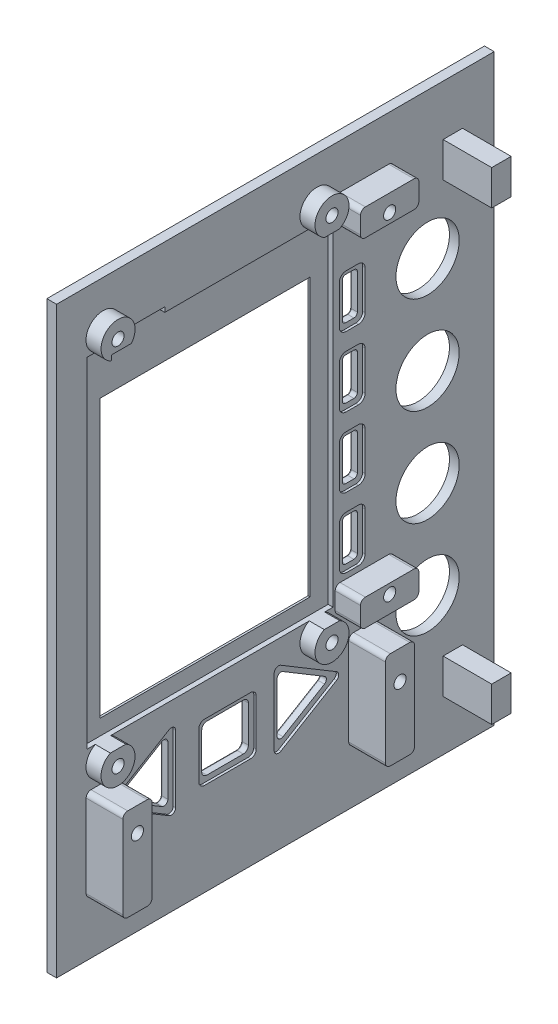
SolidWorks part; units mm, degrees
ref_plane "Front Plane" through (0, 0, 0) normal (0, 0, 1) x (1, 0, 0)
ref_plane "Top Plane" through (0, 0, 0) normal (0, 1, 0) x (1, 0, 0)
ref_plane "Right Plane" through (0, 0, 0) normal (1, 0, 0) x (0, 0, -1)
ref_plane "Plane2" through (-1175.0489, 0, 0) normal (-1, 0, 0) x (0, 0, 1)
sketch "Sketch2" plane through (-1175.0489, 0, 0) normal (-1, 0, 0) x (0, 0, 1)
  line L0 (-1289.195, -889.2833) -> (-1289.195, -789.2833) construction
  line L1 (-1204.195, -779.2833) -> (-1294.195, -779.2833)
  line L2 (-1204.195, -779.2833) -> (-1204.195, -899.2833)
  line L3 (-1204.195, -899.2833) -> (-1294.195, -899.2833)
  line L4 (-1294.195, -779.2833) -> (-1294.195, -899.2833)
  line L5 (-1289.195, -889.2833) -> (-1287.685, -889.2833) construction
  line L6 (-1289.195, -789.2833) -> (-1287.685, -789.2833) construction
  circle A0 centre (-1280.5, -869.2833) radius 6.5
  circle A1 centre (-1280.5, -849.2833) radius 6.5
  circle A2 centre (-1280.5, -829.2833) radius 6.5
  circle A3 centre (-1280.5, -809.2833) radius 6.5
  ellipse E0 centre (-1280.5, -869.2833) end of major axis (-1280.0404, -869.7429) minor radius 0.65 construction
  ellipse E1 centre (-1280.5, -849.2833) end of major axis (-1280.0404, -849.7429) minor radius 0.65 construction
  ellipse E2 centre (-1280.5, -829.2833) end of major axis (-1280.0404, -829.7429) minor radius 0.65 construction
  ellipse E3 centre (-1280.5, -809.2833) end of major axis (-1280.0404, -809.7429) minor radius 0.65 construction
  ellipse E4 centre (-1280.5, -869.2833) end of major axis (-1280.0404, -869.7429) minor radius 0.65
  ellipse E5 centre (-1280.5, -849.2833) end of major axis (-1280.0404, -849.7429) minor radius 0.65 construction
  ellipse E6 centre (-1280.5, -829.2833) end of major axis (-1280.0404, -829.7429) minor radius 0.65
  ellipse E7 centre (-1280.5, -809.2833) end of major axis (-1280.0404, -809.7429) minor radius 0.65
  dimension "D5" = 13
  dimension "D6" = 13
  dimension "D7" = 13
  dimension "D8" = 13
  dimension "D1" = 5
  dimension "D2" = 10
  dimension "D3" = 10
  dimension "D4" = 90
extrude "Boss-Extrude2" add sketch "Sketch2" along normal blind 2 contours L1 L4 L3 L2 A3 A2 A1 A0 region at (-1175.0489, -839.2833, -1247.5765)
sketch "Sketch3" plane through (-1177.0489, 0, 0) normal (-1, 0, 0) x (0, 0, 1)
  line L12 (-1214.15, -858.4833) -> (-1257.35, -858.4833) construction
  line L13 (-1257.35, -858.4833) -> (-1257.35, -801.5033) construction
  line L14 (-1214.15, -801.5033) -> (-1214.15, -858.4833) construction
  line L15 (-1257.35, -801.5033) -> (-1214.15, -801.5033) construction
  line L16 (-1214.15, -858.4833) -> (-1257.35, -858.4833)
  line L17 (-1257.35, -858.4833) -> (-1257.35, -801.5033)
  line L18 (-1214.15, -801.5033) -> (-1214.15, -858.4833)
  line L19 (-1257.35, -801.5033) -> (-1214.15, -801.5033)
extrude "tft_cutout" cut sketch "Sketch3" against normal through all
sketch "tft_inset_cutout" plane through (-1175.0489, 0, 0) normal (1, 0, 0) x (0, 0, -1)
  line L4 (1210.95, -792.3623) -> (1210.95, -861.1623) construction
  line L5 (1260.55, -792.3623) -> (1210.95, -792.3623) construction
  line L12 (1260.55, -861.1623) -> (1260.55, -792.3623) construction
  line L17 (1210.95, -861.1623) -> (1260.55, -861.1623) construction
  line L18 (1260.55, -861.1623) -> (1260.55, -792.3623) construction
  line L19 (1210.95, -861.1623) -> (1260.55, -861.1623) construction
  line L20 (1210.95, -792.3623) -> (1210.95, -861.1623) construction
  line L21 (1260.55, -792.3623) -> (1210.95, -792.3623) construction
  line L22 (1261.05, -791.8623) -> (1210.45, -791.8623)
  line L26 (1212.45, -792.3623) -> (1226.45, -792.3623)
  line L27 (1212.45, -792.3623) -> (1212.45, -790.8623)
  line L28 (1212.45, -790.8623) -> (1226.45, -790.8623)
  line L29 (1226.45, -792.3623) -> (1226.45, -790.8623)
  line L30 (1210.45, -791.8623) -> (1210.45, -861.6623)
  line L31 (1210.45, -861.6623) -> (1261.05, -861.6623)
  line L32 (1261.05, -861.6623) -> (1261.05, -791.8623)
  line M40 (1257.35, -858.4833) -> (1214.15, -858.4833)
  line M41 (1214.15, -858.4833) -> (1214.15, -801.5033)
  line M42 (1214.15, -801.5033) -> (1257.35, -801.5033)
  line M43 (1257.35, -801.5033) -> (1257.35, -858.4833)
  dimension "D3" = 1.5
  dimension "D4" = 0.5
  dimension "D1" = 14
  dimension "D2" = 1.5
extrude "Cut-Extrude2" cut sketch "tft_inset_cutout" against normal up to surface (1 mm away) contours L18 | L31 L32 L22 L29 L26 L27 L30 M43 M40 M41 M42 | L26 L29 L22 L27 | L22 L29 L28 L27 region at (-1175.0489, -826.7623, -1260.1879) region at (-1175.0489, -792.1123, -1219.45) region at (-1175.0489, -791.3623, -1219.45)
chamfer "Chamfer2" distance 1 angle 30 4 edges at (-1177.0489, -829.9933, -1257.35) (-1177.0489, -858.4833, -1235.75) (-1177.0489, -829.9933, -1214.15) (-1177.0489, -801.5033, -1235.75) first distance on face at (-1177.0489, -829.9933, -1235.75)
sketch "Sketch6" plane through (-1175.0489, 0, 0) normal (1, 0, 0) x (0, 0, -1)
  line L5 (1261.5, -863.4916) -> (1273.5, -863.4916)
  line L6 (1261.5, -863.4916) -> (1261.5, -857.9916)
  line L7 (1261.5, -857.9916) -> (1273.5, -857.9916)
  line L8 (1261.5, -863.4916) -> (1273.5, -863.4916)
  line L9 (1273.5, -863.4916) -> (1273.5, -788.4916)
  line L10 (1273.5, -788.4916) -> (1261.5, -788.4916)
  line L11 (1261.5, -788.4916) -> (1261.5, -863.4916)
  line L12 (1261.5, -863.4916) -> (1273.5, -863.4916) construction
  line L13 (1273.5, -863.4916) -> (1273.5, -788.4916) construction
  line L14 (1273.5, -788.4916) -> (1261.5, -788.4916) construction
  line L15 (1261.5, -788.4916) -> (1261.5, -863.4916) construction
  line L16 (1273.5, -863.4916) -> (1273.5, -857.9916)
  line L17 (1261.5, -788.4916) -> (1273.5, -788.4916)
  line L18 (1261.5, -788.4916) -> (1261.5, -793.9916)
  line L19 (1261.5, -793.9916) -> (1273.5, -793.9916)
  line L20 (1273.5, -788.4916) -> (1273.5, -793.9916)
  circle A0 centre (1267.5, -859.9916) radius 1.25 construction
  circle A1 centre (1267.5, -859.9916) radius 1.25 construction
  circle A2 centre (1267.5, -859.9916) radius 1.25
  circle A3 centre (1267.5, -791.9916) radius 1.25 construction
  circle A4 centre (1267.5, -791.9916) radius 1.25 construction
  circle A5 centre (1267.5, -791.9916) radius 1.25
  dimension "D2" = 2.5
  dimension "D4" = 2.5
  dimension "D3" = 2
  dimension "D5" = 2
extrude "menu_standoffs" add sketch "Sketch6" along normal up to surface (5.203 mm away)
fillet "Fillet1" radius 1 8 edges at (-1172.4474, -793.9916, -1261.5) (-1172.4474, -793.9916, -1273.5) (-1172.4474, -788.4916, -1273.5) (-1172.4474, -788.4916, -1261.5) (-1172.4474, -857.9916, -1273.5) (-1172.4474, -857.9916, -1261.5) (-1172.4474, -863.4916, -1261.5) (-1172.4474, -863.4916, -1273.5)
sketch "Sketch7" plane through (-1169.8459, 0, 0) normal (1, 0, 0) x (0, 0, -1)
  circle A0 centre (1267.5, -859.9916) radius 1.25 construction
  circle A1 centre (1267.5, -791.9916) radius 1.25 construction
  circle A2 centre (1267.5, -859.9916) radius 1.25
  circle A3 centre (1267.5, -791.9916) radius 1.25
extrude "menu_standoff_holes" [suppressed] cut sketch "Sketch7" against normal blind 5 contours A2
sketch "Sketch8" plane through (-1175.0489, 0, 0) normal (1, 0, 0) x (0, 0, -1)
  circle A0 centre (1213.75, -864.7833) radius 1.55 construction
  circle A1 centre (1257.75, -864.7833) radius 1.55 construction
  circle A2 centre (1257.75, -788.7033) radius 1.55 construction
  circle A3 centre (1213.75, -788.7036) radius 1.55 construction
  circle A4 centre (1213.75, -864.7833) radius 1.55 construction
  circle A5 centre (1257.75, -864.7833) radius 1.55 construction
  circle A6 centre (1257.75, -788.7033) radius 1.55 construction
  circle A7 centre (1213.75, -788.7036) radius 1.55 construction
  circle A8 centre (1213.75, -788.7036) radius 3.5
  circle A9 centre (1257.75, -788.7033) radius 3.5
  circle A10 centre (1257.75, -864.7833) radius 3.5
  circle A11 centre (1213.75, -864.7833) radius 3.5
  circle A12 centre (1213.75, -788.7036) radius 1.25
  circle A13 centre (1213.75, -864.7833) radius 1.25
  circle A14 centre (1257.75, -864.7833) radius 1.25
  circle A15 centre (1257.75, -788.7033) radius 1.25
  dimension "D2" = 2.5
  dimension "D1" = 7
extrude "TFT_standoffs" add sketch "Sketch8" along normal up to surface (3.09 mm away)
sketch "Sketch9" plane through (-1175.0489, 0, 0) normal (1, 0, 0) x (0, 0, -1)
  circle A0 centre (1213.75, -788.7036) radius 1.25 construction
  circle A1 centre (1213.75, -864.7833) radius 1.25 construction
  circle A2 centre (1257.75, -864.7833) radius 1.25 construction
  circle A3 centre (1257.75, -788.7033) radius 1.25 construction
  circle A4 centre (1213.75, -788.7036) radius 1.25
  circle A5 centre (1213.75, -864.7833) radius 1.25
  circle A6 centre (1257.75, -864.7833) radius 1.25
  circle A7 centre (1257.75, -788.7033) radius 1.25
extrude "TFT_standoff_holes" cut sketch "Sketch9" against normal offset from surface (1 mm away) 1 up to face at (-1177.0489, -829.9933, -1235.75)
extrude "Cut-Extrude5" cut sketch "Sketch5<3>" along normal through all contours L31 L32 L22 L29 L26 L27 L30 M43 M40 M41 M42 | L22 L29 L28 L27 | L26 L29 L22 L27 region at (-1175.0489, -826.7623, -1260.1879) region at (-1175.0489, -792.1123, -1219.45) region at (-1175.0489, -791.3623, -1219.45)
sketch "Sketch5<3>" plane through (-1175.0489, 0, 0) normal (1, 0, 0) x (0, 0, -1) same geometry as "tft_inset_cutout"
sketch "Sketch10" plane through (-1175.0489, 0, 0) normal (1, 0, 0) x (0, 0, -1)
  line L0 (1267.2535, -804.4983) -> (1267.2535, -812.4983) construction
  line L1 (1266.2535, -813.4983) -> (1263.7535, -813.4983) construction
  line L2 (1262.7535, -812.4983) -> (1262.7535, -804.4983) construction
  line L3 (1263.7535, -803.4983) -> (1266.2535, -803.4983) construction
  line L4 (1267.2535, -804.4983) -> (1267.2535, -812.4983) construction
  line L5 (1266.2535, -813.4983) -> (1263.7535, -813.4983) construction
  line L6 (1262.7535, -812.4983) -> (1262.7535, -804.4983) construction
  line L7 (1263.7535, -803.4983) -> (1266.2535, -803.4983) construction
  line L8 (1267.6535, -804.4983) -> (1267.6535, -812.4983)
  line L9 (1266.2535, -813.8983) -> (1263.7535, -813.8983)
  line L10 (1262.3535, -812.4983) -> (1262.3535, -804.4983)
  line L11 (1263.7535, -803.0983) -> (1266.2535, -803.0983)
  line L12 (1267.6535, -818.8283) -> (1267.6535, -826.8283)
  line L13 (1266.2535, -828.2283) -> (1263.7535, -828.2283)
  line L14 (1262.3535, -826.8283) -> (1262.3535, -818.8283)
  line L15 (1263.7535, -817.4283) -> (1266.2535, -817.4283)
  line L16 (1267.2535, -818.8283) -> (1267.2535, -826.8283) construction
  line L17 (1266.2535, -827.8283) -> (1263.7535, -827.8283) construction
  line L18 (1262.7535, -826.8283) -> (1262.7535, -818.8283) construction
  line L19 (1263.7535, -817.8283) -> (1266.2535, -817.8283) construction
  line L20 (1267.6535, -833.1583) -> (1267.6535, -841.1583)
  line L21 (1266.2535, -842.5583) -> (1263.7535, -842.5583)
  line L22 (1262.3535, -841.1583) -> (1262.3535, -833.1583)
  line L23 (1263.7535, -831.7583) -> (1266.2535, -831.7583)
  line L24 (1267.2535, -833.1583) -> (1267.2535, -841.1583) construction
  line L25 (1266.2535, -842.1583) -> (1263.7535, -842.1583) construction
  line L26 (1262.7535, -841.1583) -> (1262.7535, -833.1583) construction
  line L27 (1263.7535, -832.1583) -> (1266.2535, -832.1583) construction
  line L28 (1267.6535, -847.4883) -> (1267.6535, -855.4883)
  line L29 (1266.2535, -856.8883) -> (1263.7535, -856.8883)
  line L30 (1262.3535, -855.4883) -> (1262.3535, -847.4883)
  line L31 (1263.7535, -846.0883) -> (1266.2535, -846.0883)
  line L32 (1267.2535, -847.4883) -> (1267.2535, -855.4883) construction
  line L33 (1266.2535, -856.4883) -> (1263.7535, -856.4883) construction
  line L34 (1262.7535, -855.4883) -> (1262.7535, -847.4883) construction
  line L35 (1263.7535, -846.4883) -> (1266.2535, -846.4883) construction
  arc A0 (1267.2535, -804.4983) -> (1266.2535, -803.4983) centre (1266.2535, -804.4983) ccw construction
  arc A1 (1266.2535, -813.4983) -> (1267.2535, -812.4983) centre (1266.2535, -812.4983) ccw construction
  arc A2 (1262.7535, -812.4983) -> (1263.7535, -813.4983) centre (1263.7535, -812.4983) ccw construction
  arc A3 (1263.7535, -803.4983) -> (1262.7535, -804.4983) centre (1263.7535, -804.4983) ccw construction
  arc A4 (1267.2535, -804.4983) -> (1266.2535, -803.4983) centre (1266.2535, -804.4983) ccw construction
  arc A5 (1266.2535, -813.4983) -> (1267.2535, -812.4983) centre (1266.2535, -812.4983) ccw construction
  arc A6 (1262.7535, -812.4983) -> (1263.7535, -813.4983) centre (1263.7535, -812.4983) ccw construction
  arc A7 (1263.7535, -803.4983) -> (1262.7535, -804.4983) centre (1263.7535, -804.4983) ccw construction
  arc A8 (1266.2535, -813.8983) -> (1267.6535, -812.4983) centre (1266.2535, -812.4983) ccw
  arc A9 (1262.3535, -812.4983) -> (1263.7535, -813.8983) centre (1263.7535, -812.4983) ccw
  arc A10 (1263.7535, -803.0983) -> (1262.3535, -804.4983) centre (1263.7535, -804.4983) ccw
  arc A11 (1267.6535, -804.4983) -> (1266.2535, -803.0983) centre (1266.2535, -804.4983) ccw
  arc A12 (1266.2535, -828.2283) -> (1267.6535, -826.8283) centre (1266.2535, -826.8283) ccw
  arc A13 (1262.3535, -826.8283) -> (1263.7535, -828.2283) centre (1263.7535, -826.8283) ccw
  arc A14 (1263.7535, -817.4283) -> (1262.3535, -818.8283) centre (1263.7535, -818.8283) ccw
  arc A15 (1267.6535, -818.8283) -> (1266.2535, -817.4283) centre (1266.2535, -818.8283) ccw
  arc A16 (1267.2535, -818.8283) -> (1266.2535, -817.8283) centre (1266.2535, -818.8283) ccw construction
  arc A17 (1266.2535, -827.8283) -> (1267.2535, -826.8283) centre (1266.2535, -826.8283) ccw construction
  arc A18 (1262.7535, -826.8283) -> (1263.7535, -827.8283) centre (1263.7535, -826.8283) ccw construction
  arc A19 (1263.7535, -817.8283) -> (1262.7535, -818.8283) centre (1263.7535, -818.8283) ccw construction
  arc A20 (1266.2535, -842.5583) -> (1267.6535, -841.1583) centre (1266.2535, -841.1583) ccw
  arc A21 (1262.3535, -841.1583) -> (1263.7535, -842.5583) centre (1263.7535, -841.1583) ccw
  arc A22 (1263.7535, -831.7583) -> (1262.3535, -833.1583) centre (1263.7535, -833.1583) ccw
  arc A23 (1267.6535, -833.1583) -> (1266.2535, -831.7583) centre (1266.2535, -833.1583) ccw
  arc A24 (1267.2535, -833.1583) -> (1266.2535, -832.1583) centre (1266.2535, -833.1583) ccw construction
  arc A25 (1266.2535, -842.1583) -> (1267.2535, -841.1583) centre (1266.2535, -841.1583) ccw construction
  arc A26 (1262.7535, -841.1583) -> (1263.7535, -842.1583) centre (1263.7535, -841.1583) ccw construction
  arc A27 (1263.7535, -832.1583) -> (1262.7535, -833.1583) centre (1263.7535, -833.1583) ccw construction
  arc A28 (1266.2535, -856.8883) -> (1267.6535, -855.4883) centre (1266.2535, -855.4883) ccw
  arc A29 (1262.3535, -855.4883) -> (1263.7535, -856.8883) centre (1263.7535, -855.4883) ccw
  arc A30 (1263.7535, -846.0883) -> (1262.3535, -847.4883) centre (1263.7535, -847.4883) ccw
  arc A31 (1267.6535, -847.4883) -> (1266.2535, -846.0883) centre (1266.2535, -847.4883) ccw
  arc A32 (1267.2535, -847.4883) -> (1266.2535, -846.4883) centre (1266.2535, -847.4883) ccw construction
  arc A33 (1266.2535, -856.4883) -> (1267.2535, -855.4883) centre (1266.2535, -855.4883) ccw construction
  arc A34 (1262.7535, -855.4883) -> (1263.7535, -856.4883) centre (1263.7535, -855.4883) ccw construction
  arc A35 (1263.7535, -846.4883) -> (1262.7535, -847.4883) centre (1263.7535, -847.4883) ccw construction
  dimension "D1" = 0.4
  dimension "D2" = 4
extrude "menu_panel_inset" cut sketch "Sketch10" against normal offset from surface 1.5 and the other way through all up to face at (-1177.0489, -829.9933, -1235.75)
sketch "Sketch11" plane through (-1177.0489, 0, 0) normal (-1, 0, 0) x (0, 0, 1)
  line L0 (-1265.8535, -812.4983) -> (-1264.1535, -812.4983) construction
  line L1 (-1266.2535, -804.8983) -> (-1266.2535, -812.0983) construction
  line L2 (-1265.8535, -804.4983) -> (-1264.1535, -804.4983) construction
  line L3 (-1263.7535, -804.8983) -> (-1263.7535, -812.0983) construction
  line L4 (-1265.8535, -812.4983) -> (-1264.1535, -812.4983) construction
  line L5 (-1266.2535, -804.8983) -> (-1266.2535, -812.0983) construction
  line L6 (-1265.8535, -804.4983) -> (-1264.1535, -804.4983) construction
  line L7 (-1263.7535, -804.8983) -> (-1263.7535, -812.0983) construction
  line L8 (-1263.4535, -804.8983) -> (-1263.4535, -812.0983)
  line L9 (-1265.8535, -812.7983) -> (-1264.1535, -812.7983)
  line L10 (-1266.5535, -804.8983) -> (-1266.5535, -812.0983)
  line L11 (-1265.8535, -804.1983) -> (-1264.1535, -804.1983)
  line L12 (-1263.4535, -819.2283) -> (-1263.4535, -826.4283)
  line L13 (-1265.8535, -827.1283) -> (-1264.1535, -827.1283)
  line L14 (-1266.5535, -819.2283) -> (-1266.5535, -826.4283)
  line L15 (-1265.8535, -818.5283) -> (-1264.1535, -818.5283)
  line L16 (-1265.8535, -826.8283) -> (-1264.1535, -826.8283) construction
  line L17 (-1266.2535, -819.2283) -> (-1266.2535, -826.4283) construction
  line L18 (-1265.8535, -818.8283) -> (-1264.1535, -818.8283) construction
  line L19 (-1263.7535, -819.2283) -> (-1263.7535, -826.4283) construction
  line L20 (-1263.4535, -833.5583) -> (-1263.4535, -840.7583)
  line L21 (-1265.8535, -841.4583) -> (-1264.1535, -841.4583)
  line L22 (-1266.5535, -833.5583) -> (-1266.5535, -840.7583)
  line L23 (-1265.8535, -832.8583) -> (-1264.1535, -832.8583)
  line L24 (-1265.8535, -841.1583) -> (-1264.1535, -841.1583) construction
  line L25 (-1266.2535, -833.5583) -> (-1266.2535, -840.7583) construction
  line L26 (-1265.8535, -833.1583) -> (-1264.1535, -833.1583) construction
  line L27 (-1263.7535, -833.5583) -> (-1263.7535, -840.7583) construction
  line L28 (-1263.4535, -847.8883) -> (-1263.4535, -855.0883)
  line L29 (-1265.8535, -855.7883) -> (-1264.1535, -855.7883)
  line L30 (-1266.5535, -847.8883) -> (-1266.5535, -855.0883)
  line L31 (-1265.8535, -847.1883) -> (-1264.1535, -847.1883)
  line L32 (-1265.8535, -855.4883) -> (-1264.1535, -855.4883) construction
  line L33 (-1266.2535, -847.8883) -> (-1266.2535, -855.0883) construction
  line L34 (-1265.8535, -847.4883) -> (-1264.1535, -847.4883) construction
  line L35 (-1263.7535, -847.8883) -> (-1263.7535, -855.0883) construction
  arc A0 (-1264.1535, -812.4983) -> (-1263.7535, -812.0983) centre (-1264.1535, -812.0983) ccw construction
  arc A1 (-1266.2535, -812.0983) -> (-1265.8535, -812.4983) centre (-1265.8535, -812.0983) ccw construction
  arc A2 (-1265.8535, -804.4983) -> (-1266.2535, -804.8983) centre (-1265.8535, -804.8983) ccw construction
  arc A3 (-1263.7535, -804.8983) -> (-1264.1535, -804.4983) centre (-1264.1535, -804.8983) ccw construction
  arc A4 (-1264.1535, -812.4983) -> (-1263.7535, -812.0983) centre (-1264.1535, -812.0983) ccw construction
  arc A5 (-1266.2535, -812.0983) -> (-1265.8535, -812.4983) centre (-1265.8535, -812.0983) ccw construction
  arc A6 (-1265.8535, -804.4983) -> (-1266.2535, -804.8983) centre (-1265.8535, -804.8983) ccw construction
  arc A7 (-1263.7535, -804.8983) -> (-1264.1535, -804.4983) centre (-1264.1535, -804.8983) ccw construction
  arc A8 (-1264.1535, -812.7983) -> (-1263.4535, -812.0983) centre (-1264.1535, -812.0983) ccw
  arc A9 (-1266.5535, -812.0983) -> (-1265.8535, -812.7983) centre (-1265.8535, -812.0983) ccw
  arc A10 (-1265.8535, -804.1983) -> (-1266.5535, -804.8983) centre (-1265.8535, -804.8983) ccw
  arc A11 (-1263.4535, -804.8983) -> (-1264.1535, -804.1983) centre (-1264.1535, -804.8983) ccw
  arc A12 (-1264.1535, -827.1283) -> (-1263.4535, -826.4283) centre (-1264.1535, -826.4283) ccw
  arc A13 (-1266.5535, -826.4283) -> (-1265.8535, -827.1283) centre (-1265.8535, -826.4283) ccw
  arc A14 (-1265.8535, -818.5283) -> (-1266.5535, -819.2283) centre (-1265.8535, -819.2283) ccw
  arc A15 (-1263.4535, -819.2283) -> (-1264.1535, -818.5283) centre (-1264.1535, -819.2283) ccw
  arc A16 (-1264.1535, -826.8283) -> (-1263.7535, -826.4283) centre (-1264.1535, -826.4283) ccw construction
  arc A17 (-1266.2535, -826.4283) -> (-1265.8535, -826.8283) centre (-1265.8535, -826.4283) ccw construction
  arc A18 (-1265.8535, -818.8283) -> (-1266.2535, -819.2283) centre (-1265.8535, -819.2283) ccw construction
  arc A19 (-1263.7535, -819.2283) -> (-1264.1535, -818.8283) centre (-1264.1535, -819.2283) ccw construction
  arc A20 (-1264.1535, -841.4583) -> (-1263.4535, -840.7583) centre (-1264.1535, -840.7583) ccw
  arc A21 (-1266.5535, -840.7583) -> (-1265.8535, -841.4583) centre (-1265.8535, -840.7583) ccw
  arc A22 (-1265.8535, -832.8583) -> (-1266.5535, -833.5583) centre (-1265.8535, -833.5583) ccw
  arc A23 (-1263.4535, -833.5583) -> (-1264.1535, -832.8583) centre (-1264.1535, -833.5583) ccw
  arc A24 (-1264.1535, -841.1583) -> (-1263.7535, -840.7583) centre (-1264.1535, -840.7583) ccw construction
  arc A25 (-1266.2535, -840.7583) -> (-1265.8535, -841.1583) centre (-1265.8535, -840.7583) ccw construction
  arc A26 (-1265.8535, -833.1583) -> (-1266.2535, -833.5583) centre (-1265.8535, -833.5583) ccw construction
  arc A27 (-1263.7535, -833.5583) -> (-1264.1535, -833.1583) centre (-1264.1535, -833.5583) ccw construction
  arc A28 (-1264.1535, -855.7883) -> (-1263.4535, -855.0883) centre (-1264.1535, -855.0883) ccw
  arc A29 (-1266.5535, -855.0883) -> (-1265.8535, -855.7883) centre (-1265.8535, -855.0883) ccw
  arc A30 (-1265.8535, -847.1883) -> (-1266.5535, -847.8883) centre (-1265.8535, -847.8883) ccw
  arc A31 (-1263.4535, -847.8883) -> (-1264.1535, -847.1883) centre (-1264.1535, -847.8883) ccw
  arc A32 (-1264.1535, -855.4883) -> (-1263.7535, -855.0883) centre (-1264.1535, -855.0883) ccw construction
  arc A33 (-1266.2535, -855.0883) -> (-1265.8535, -855.4883) centre (-1265.8535, -855.0883) ccw construction
  arc A34 (-1265.8535, -847.4883) -> (-1266.2535, -847.8883) centre (-1265.8535, -847.8883) ccw construction
  arc A35 (-1263.7535, -847.8883) -> (-1264.1535, -847.4883) centre (-1264.1535, -847.8883) ccw construction
  dimension "D1" = 0.3
  dimension "D2" = 4
extrude "menu_panel_cutout" cut sketch "Sketch11" against normal through all
fillet "Fillet2" radius 0.25 32 edges at (-1177.0489, -808.4983, -1263.4535) (-1177.0489, -812.5933, -1263.6586) (-1177.0489, -812.7983, -1265.0035) (-1177.0489, -812.5933, -1266.3485) (-1177.0489, -808.4983, -1266.5535) (-1177.0489, -804.4033, -1266.3485) (-1177.0489, -804.1983, -1265.0035) (-1177.0489, -827.1283, -1265.0035) (-1177.0489, -826.9233, -1266.3485) (-1177.0489, -822.8283, -1266.5535) (-1177.0489, -818.7333, -1266.3485) (-1177.0489, -818.5283, -1265.0035) (-1177.0489, -818.7333, -1263.6586) (-1177.0489, -822.8283, -1263.4535) (-1177.0489, -841.4583, -1265.0035) (-1177.0489, -841.2533, -1266.3485) (-1177.0489, -837.1583, -1266.5535) (-1177.0489, -833.0633, -1266.3485) (-1177.0489, -832.8583, -1265.0035) (-1177.0489, -833.0633, -1263.6586) (-1177.0489, -837.1583, -1263.4535) (-1177.0489, -851.4883, -1263.4535) (-1177.0489, -855.5833, -1263.6586) (-1177.0489, -855.7883, -1265.0035) (-1177.0489, -855.5833, -1266.3485) (-1177.0489, -851.4883, -1266.5535) (-1177.0489, -847.3933, -1266.3485) (-1177.0489, -847.1883, -1265.0035) (-1177.0489, -804.4033, -1263.6586) (-1177.0489, -826.9233, -1263.6586) (-1177.0489, -841.2533, -1263.6586) (-1177.0489, -847.3933, -1263.6586)
sketch "Sketch12" plane through (-1175.0489, 0, 0) normal (1, 0, 0) x (0, 0, -1)
  line L0 (1270.2797, -888.2833) -> (1210.2797, -888.2833) construction
  line L1 (1270.2797, -868.2833) -> (1264.2797, -868.2833)
  line L2 (1270.2797, -868.2833) -> (1270.2797, -888.2833)
  line L3 (1270.2797, -888.2833) -> (1264.2797, -888.2833)
  line L4 (1264.2797, -868.2833) -> (1264.2797, -888.2833)
  line L6 (1210.2797, -888.2833) -> (1216.2797, -888.2833)
  line L7 (1210.2797, -888.2833) -> (1210.2797, -869.2833)
  line L8 (1210.2797, -869.2833) -> (1216.2797, -869.2833)
  line L9 (1216.2797, -888.2833) -> (1216.2797, -869.2833)
  line L10 (1210.2797, -868.2833) -> (1270.2797, -868.2833) construction
  circle A0 centre (1267.2797, -874.2833) radius 1.25
  circle A1 centre (1213.2797, -874.2833) radius 1.25
  point P15 (1215.7858, -869.1225)
  point P20 (0, 0)
  dimension "D2" = 2.5
  dimension "D4" = 2.5
  dimension "D1" = 6
  dimension "D3" = 6
  dimension "D5" = 1
extrude "selector_standoffs" add sketch "Sketch12" along normal up to surface (7.55 mm away) contours L6 L9 L8 L7 A1 | L1 L4 L3 L2 A0 region at (-1175.0489, -878.4539, -1267.2797) region at (-1175.0489, -878.9858, -1213.2797)
fillet "Fillet3" radius 1 8 edges at (-1171.2739, -888.2833, -1270.2797) (-1171.2739, -868.2833, -1270.2797) (-1171.2739, -868.2833, -1264.2797) (-1171.2739, -888.2833, -1264.2797) (-1171.2739, -888.2833, -1216.2797) (-1171.2739, -888.2833, -1210.2797) (-1171.2739, -869.2833, -1210.2797) (-1171.2739, -869.2833, -1216.2797)
sketch "Sketch13" plane through (-1175.0489, 0, 0) normal (1, 0, 0) x (0, 0, -1)
  line L0 (1218.0014, -874.7192) -> (1226.5296, -879.8361) construction
  line L1 (1227.2868, -879.4073) -> (1227.2868, -869.1735) construction
  line L2 (1226.5296, -868.7448) -> (1218.0014, -873.8617) construction
  line L3 (1234.85, -870.5404) -> (1234.85, -878.0404) construction
  line L4 (1235.6, -878.7904) -> (1243.1, -878.7904) construction
  line L5 (1243.1, -869.7904) -> (1235.6, -869.7904) construction
  line L6 (1243.85, -878.0404) -> (1243.85, -870.5404) construction
  line L7 (1259.6354, -873.8617) -> (1251.1072, -868.7448) construction
  line L8 (1250.35, -869.1735) -> (1250.35, -879.4073) construction
  line L9 (1251.1072, -879.8361) -> (1259.6354, -874.7192) construction
  line L10 (1218.0014, -874.7192) -> (1226.5296, -879.8361) construction
  line L11 (1227.2868, -879.4073) -> (1227.2868, -869.1735) construction
  line L12 (1226.5296, -868.7448) -> (1218.0014, -873.8617) construction
  line L13 (1234.85, -870.5404) -> (1234.85, -878.0404) construction
  line L14 (1235.6, -878.7904) -> (1243.1, -878.7904) construction
  line L15 (1243.1, -869.7904) -> (1235.6, -869.7904) construction
  line L16 (1243.85, -878.0404) -> (1243.85, -870.5404) construction
  line L17 (1259.6354, -873.8617) -> (1251.1072, -868.7448) construction
  line L18 (1250.35, -869.1735) -> (1250.35, -879.4073) construction
  line L19 (1251.1072, -879.8361) -> (1259.6354, -874.7192) construction
  line L20 (1217.847, -874.9764) -> (1226.3752, -880.0933)
  line L21 (1227.5868, -879.4073) -> (1227.5868, -869.1735)
  line L22 (1226.3752, -868.4875) -> (1217.847, -873.6044)
  line L23 (1234.55, -870.5404) -> (1234.55, -878.0404)
  line L24 (1235.6, -879.0904) -> (1243.1, -879.0904)
  line L25 (1244.15, -878.0404) -> (1244.15, -870.5404)
  line L26 (1243.1, -869.4904) -> (1235.6, -869.4904)
  line L27 (1259.7898, -873.6044) -> (1251.2616, -868.4875)
  line L28 (1250.05, -869.1735) -> (1250.05, -879.4073)
  line L29 (1251.2616, -880.0933) -> (1259.7898, -874.9764)
  arc A0 (1218.0014, -873.8617) -> (1218.0014, -874.7192) centre (1218.2586, -874.2904) ccw construction
  arc A1 (1226.5296, -879.8361) -> (1227.2868, -879.4073) centre (1226.7868, -879.4073) ccw construction
  arc A2 (1227.2868, -869.1735) -> (1226.5296, -868.7448) centre (1226.7868, -869.1735) ccw construction
  arc A3 (1235.6, -869.7904) -> (1234.85, -870.5404) centre (1235.6, -870.5404) ccw construction
  arc A4 (1234.85, -878.0404) -> (1235.6, -878.7904) centre (1235.6, -878.0404) ccw construction
  arc A5 (1243.1, -878.7904) -> (1243.85, -878.0404) centre (1243.1, -878.0404) ccw construction
  arc A6 (1243.85, -870.5404) -> (1243.1, -869.7904) centre (1243.1, -870.5404) ccw construction
  arc A7 (1259.6354, -874.7192) -> (1259.6354, -873.8617) centre (1259.3782, -874.2904) ccw construction
  arc A8 (1251.1072, -868.7448) -> (1250.35, -869.1735) centre (1250.85, -869.1735) ccw construction
  arc A9 (1250.35, -879.4073) -> (1251.1072, -879.8361) centre (1250.85, -879.4073) ccw construction
  arc A10 (1218.0014, -873.8617) -> (1218.0014, -874.7192) centre (1218.2586, -874.2904) ccw construction
  arc A11 (1226.5296, -879.8361) -> (1227.2868, -879.4073) centre (1226.7868, -879.4073) ccw construction
  arc A12 (1227.2868, -869.1735) -> (1226.5296, -868.7448) centre (1226.7868, -869.1735) ccw construction
  arc A13 (1235.6, -869.7904) -> (1234.85, -870.5404) centre (1235.6, -870.5404) ccw construction
  arc A14 (1234.85, -878.0404) -> (1235.6, -878.7904) centre (1235.6, -878.0404) ccw construction
  arc A15 (1243.1, -878.7904) -> (1243.85, -878.0404) centre (1243.1, -878.0404) ccw construction
  arc A16 (1243.85, -870.5404) -> (1243.1, -869.7904) centre (1243.1, -870.5404) ccw construction
  arc A17 (1259.6354, -874.7192) -> (1259.6354, -873.8617) centre (1259.3782, -874.2904) ccw construction
  arc A18 (1251.1072, -868.7448) -> (1250.35, -869.1735) centre (1250.85, -869.1735) ccw construction
  arc A19 (1250.35, -879.4073) -> (1251.1072, -879.8361) centre (1250.85, -879.4073) ccw construction
  arc A20 (1226.3752, -880.0933) -> (1227.5868, -879.4073) centre (1226.7868, -879.4073) ccw
  arc A21 (1227.5868, -869.1735) -> (1226.3752, -868.4875) centre (1226.7868, -869.1735) ccw
  arc A22 (1217.847, -873.6044) -> (1217.847, -874.9764) centre (1218.2586, -874.2904) ccw
  arc A23 (1234.55, -878.0404) -> (1235.6, -879.0904) centre (1235.6, -878.0404) ccw
  arc A24 (1243.1, -879.0904) -> (1244.15, -878.0404) centre (1243.1, -878.0404) ccw
  arc A25 (1244.15, -870.5404) -> (1243.1, -869.4904) centre (1243.1, -870.5404) ccw
  arc A26 (1235.6, -869.4904) -> (1234.55, -870.5404) centre (1235.6, -870.5404) ccw
  arc A27 (1251.2616, -868.4875) -> (1250.05, -869.1735) centre (1250.85, -869.1735) ccw
  arc A28 (1250.05, -879.4073) -> (1251.2616, -880.0933) centre (1250.85, -879.4073) ccw
  arc A29 (1259.7898, -874.9764) -> (1259.7898, -873.6044) centre (1259.3782, -874.2904) ccw
  dimension "D1" = 0.3
  dimension "D2" = 0.3
  dimension "D3" = 0.3
extrude "selector_cutout" cut sketch "Sketch13" against normal through all
fillet "Fillet4" radius 0.25 20 edges at (-1177.0489, -879.0904, -1239.35) (-1177.0489, -878.7829, -1234.8575) (-1177.0489, -874.2904, -1234.55) (-1177.0489, -869.798, -1234.8575) (-1177.0489, -869.4904, -1239.35) (-1177.0489, -869.798, -1243.8424) (-1177.0489, -874.2904, -1244.15) (-1177.0489, -868.4774, -1250.4558) (-1177.0489, -871.046, -1255.5257) (-1177.0489, -874.2904, -1260.1782) (-1177.0489, -877.5349, -1255.5257) (-1177.0489, -880.1035, -1250.4558) (-1177.0489, -878.7829, -1243.8424) (-1177.0489, -874.2904, -1250.05) (-1177.0489, -877.5349, -1222.1111) (-1177.0489, -874.2904, -1217.4586) (-1177.0489, -871.046, -1222.1111) (-1177.0489, -868.4774, -1227.181) (-1177.0489, -874.2904, -1227.5868) (-1177.0489, -880.1035, -1227.181)
sketch "Sketch17" plane through (-1175.0489, 0, 0) normal (1, 0, 0) x (0, 0, -1)
  line L18 (1220.3082, -871.3114) -> (1216.0577, -873.8617) construction
  line L19 (1216.0577, -874.7192) -> (1220.3082, -877.2694) construction
  line L20 (1220.1868, -877.0551) -> (1220.1868, -871.5258) construction
  line L21 (1228.2868, -881.1735) -> (1228.2868, -867.4073) construction
  line L22 (1227.5296, -866.9786) -> (1220.4505, -871.226) construction
  line L23 (1220.5791, -871.1904) -> (1226.1368, -871.1904) construction
  line L24 (1226.3868, -871.4404) -> (1226.3868, -877.1404) construction
  line L25 (1226.1368, -877.3904) -> (1220.5791, -877.3904) construction
  line L26 (1220.4505, -877.3548) -> (1227.5296, -881.6023) construction
  line L27 (1220.3082, -871.3114) -> (1216.0577, -873.8617) construction
  line L28 (1216.0577, -874.7192) -> (1220.3082, -877.2694) construction
  line L29 (1220.1868, -877.0551) -> (1220.1868, -871.5258) construction
  line L30 (1228.2868, -881.1735) -> (1228.2868, -867.4073) construction
  line L31 (1257.3286, -877.2694) -> (1261.5791, -874.7192) construction
  line L32 (1261.5791, -873.8617) -> (1257.3286, -871.3114) construction
  line L33 (1257.45, -871.5258) -> (1257.45, -877.0551) construction
  line L34 (1249.35, -867.4073) -> (1249.35, -881.1735) construction
  line L35 (1250.1072, -881.6023) -> (1257.1863, -877.3548) construction
  line L36 (1257.0577, -877.3904) -> (1251.5, -877.3904) construction
  line L37 (1251.25, -877.1404) -> (1251.25, -871.4404) construction
  line L38 (1251.5, -871.1904) -> (1257.0577, -871.1904) construction
  line L39 (1257.1863, -871.226) -> (1250.1072, -866.9786) construction
  line L40 (1233.85, -869.5404) -> (1233.85, -879.0404) construction
  line L41 (1234.6, -879.7904) -> (1244.1, -879.7904) construction
  line L42 (1244.85, -879.0404) -> (1244.85, -869.5404) construction
  line L43 (1244.1, -868.7904) -> (1234.6, -868.7904) construction
  line L44 (1257.3286, -877.2694) -> (1261.5791, -874.7192) construction
  line L45 (1261.5791, -873.8617) -> (1257.3286, -871.3114) construction
  line L46 (1257.45, -871.5258) -> (1257.45, -877.0551) construction
  line L47 (1249.35, -867.4073) -> (1249.35, -881.1735) construction
  line L48 (1250.1072, -881.6023) -> (1257.1863, -877.3548) construction
  line L49 (1257.0577, -877.3904) -> (1251.5, -877.3904) construction
  line L50 (1251.25, -877.1404) -> (1251.25, -871.4404) construction
  line L51 (1251.5, -871.1904) -> (1257.0577, -871.1904) construction
  line L52 (1257.1863, -871.226) -> (1250.1072, -866.9786) construction
  line L53 (1233.85, -869.5404) -> (1233.85, -879.0404) construction
  line L54 (1234.6, -879.7904) -> (1244.1, -879.7904) construction
  line L55 (1244.85, -879.0404) -> (1244.85, -869.5404) construction
  line L56 (1244.1, -868.7904) -> (1234.6, -868.7904) construction
  line L57 (1257.1863, -877.3548) -> (1257.3286, -877.2694)
  line L58 (1257.3286, -871.3114) -> (1257.1863, -871.226)
  line L59 (1227.5296, -866.9786) -> (1220.4505, -871.226) construction
  line L60 (1220.5791, -871.1904) -> (1226.1368, -871.1904) construction
  line L61 (1226.3868, -871.4404) -> (1226.3868, -877.1404) construction
  line L62 (1226.1368, -877.3904) -> (1220.5791, -877.3904) construction
  line L63 (1220.4505, -877.3548) -> (1227.5296, -881.6023) construction
  line L64 (1220.3082, -871.3114) -> (1220.4505, -871.226)
  line L65 (1220.4505, -877.3548) -> (1220.3082, -877.2694)
  line L66 (1257.3921, -877.6978) -> (1257.5344, -877.6124)
  line L67 (1257.5344, -870.9684) -> (1257.3921, -870.883)
  line L68 (1220.514, -871.6544) -> (1220.6563, -871.569)
  line L69 (1220.6563, -877.0118) -> (1220.514, -876.9264)
  line L70 (1220.1024, -870.9684) -> (1215.8519, -873.5187)
  line L71 (1215.8519, -875.0622) -> (1220.1024, -877.6124)
  line L72 (1220.5868, -876.9824) -> (1220.5868, -871.5984)
  line L73 (1220.2447, -877.6978) -> (1227.3238, -881.9453)
  line L74 (1228.6868, -881.1735) -> (1228.6868, -867.4073)
  line L75 (1227.3238, -866.6356) -> (1220.2447, -870.883)
  line L76 (1257.5344, -877.6124) -> (1261.7849, -875.0622)
  line L77 (1261.7849, -873.5187) -> (1257.5344, -870.9684)
  line L78 (1257.05, -871.5984) -> (1257.05, -876.9824)
  line L79 (1257.3921, -870.883) -> (1250.313, -866.6356)
  line L80 (1248.95, -867.4073) -> (1248.95, -881.1735)
  line L81 (1250.313, -881.9453) -> (1257.3921, -877.6978)
  line L82 (1257.0213, -876.9904) -> (1251.65, -876.9904)
  line L83 (1251.65, -876.9904) -> (1251.65, -871.5904)
  line L84 (1251.65, -871.5904) -> (1257.0213, -871.5904)
  line L85 (1233.45, -869.5404) -> (1233.45, -879.0404)
  line L86 (1234.6, -880.1904) -> (1244.1, -880.1904)
  line L87 (1245.25, -879.0404) -> (1245.25, -869.5404)
  line L88 (1244.1, -868.3904) -> (1234.6, -868.3904)
  line L89 (1220.6155, -871.5904) -> (1225.9868, -871.5904)
  line L90 (1225.9868, -871.5904) -> (1225.9868, -876.9904)
  line L91 (1225.9868, -876.9904) -> (1220.6155, -876.9904)
  line L92 (1220.1024, -877.6124) -> (1220.2447, -877.6978)
  line L93 (1220.2447, -870.883) -> (1220.1024, -870.9684)
  arc A18 (1216.0577, -873.8617) -> (1216.0577, -874.7192) centre (1216.315, -874.2904) ccw construction
  arc A19 (1220.1868, -877.0551) -> (1220.3082, -877.2694) centre (1220.4368, -877.0551) ccw construction
  arc A20 (1220.3082, -871.3114) -> (1220.1868, -871.5258) centre (1220.4368, -871.5258) ccw construction
  arc A21 (1228.2868, -867.4073) -> (1227.5296, -866.9786) centre (1227.7868, -867.4073) ccw construction
  arc A22 (1220.5791, -871.1904) -> (1220.4505, -871.226) centre (1220.5791, -871.4404) ccw construction
  arc A23 (1226.3868, -871.4404) -> (1226.1368, -871.1904) centre (1226.1368, -871.4404) ccw construction
  arc A24 (1226.1368, -877.3904) -> (1226.3868, -877.1404) centre (1226.1368, -877.1404) ccw construction
  arc A25 (1220.4505, -877.3548) -> (1220.5791, -877.3904) centre (1220.5791, -877.1404) ccw construction
  arc A26 (1227.5296, -881.6023) -> (1228.2868, -881.1735) centre (1227.7868, -881.1735) ccw construction
  arc A27 (1261.5791, -874.7192) -> (1261.5791, -873.8617) centre (1261.3218, -874.2904) ccw construction
  arc A28 (1257.45, -871.5258) -> (1257.3286, -871.3114) centre (1257.2, -871.5258) ccw construction
  arc A29 (1257.3286, -877.2694) -> (1257.45, -877.0551) centre (1257.2, -877.0551) ccw construction
  arc A30 (1249.35, -881.1735) -> (1250.1072, -881.6023) centre (1249.85, -881.1735) ccw construction
  arc A31 (1257.0577, -877.3904) -> (1257.1863, -877.3548) centre (1257.0577, -877.1404) ccw construction
  arc A32 (1251.25, -877.1404) -> (1251.5, -877.3904) centre (1251.5, -877.1404) ccw construction
  arc A33 (1251.5, -871.1904) -> (1251.25, -871.4404) centre (1251.5, -871.4404) ccw construction
  arc A34 (1257.1863, -871.226) -> (1257.0577, -871.1904) centre (1257.0577, -871.4404) ccw construction
  arc A35 (1250.1072, -866.9786) -> (1249.35, -867.4073) centre (1249.85, -867.4073) ccw construction
  arc A36 (1233.85, -879.0404) -> (1234.6, -879.7904) centre (1234.6, -879.0404) ccw construction
  arc A37 (1244.1, -879.7904) -> (1244.85, -879.0404) centre (1244.1, -879.0404) ccw construction
  arc A38 (1244.85, -869.5404) -> (1244.1, -868.7904) centre (1244.1, -869.5404) ccw construction
  arc A39 (1234.6, -868.7904) -> (1233.85, -869.5404) centre (1234.6, -869.5404) ccw construction
  arc A40 (1261.5791, -874.7192) -> (1261.5791, -873.8617) centre (1261.3218, -874.2904) ccw construction
  arc A41 (1257.45, -871.5258) -> (1257.3286, -871.3114) centre (1257.2, -871.5258) ccw construction
  arc A42 (1257.3286, -877.2694) -> (1257.45, -877.0551) centre (1257.2, -877.0551) ccw construction
  arc A43 (1249.35, -881.1735) -> (1250.1072, -881.6023) centre (1249.85, -881.1735) ccw construction
  arc A44 (1257.0577, -877.3904) -> (1257.1863, -877.3548) centre (1257.0577, -877.1404) ccw construction
  arc A45 (1251.25, -877.1404) -> (1251.5, -877.3904) centre (1251.5, -877.1404) ccw construction
  arc A46 (1251.5, -871.1904) -> (1251.25, -871.4404) centre (1251.5, -871.4404) ccw construction
  arc A47 (1257.1863, -871.226) -> (1257.0577, -871.1904) centre (1257.0577, -871.4404) ccw construction
  arc A48 (1250.1072, -866.9786) -> (1249.35, -867.4073) centre (1249.85, -867.4073) ccw construction
  arc A49 (1233.85, -879.0404) -> (1234.6, -879.7904) centre (1234.6, -879.0404) ccw construction
  arc A50 (1244.1, -879.7904) -> (1244.85, -879.0404) centre (1244.1, -879.0404) ccw construction
  arc A51 (1244.85, -869.5404) -> (1244.1, -868.7904) centre (1244.1, -869.5404) ccw construction
  arc A52 (1234.6, -868.7904) -> (1233.85, -869.5404) centre (1234.6, -869.5404) ccw construction
  arc A53 (1216.0577, -873.8617) -> (1216.0577, -874.7192) centre (1216.315, -874.2904) ccw construction
  arc A54 (1220.1868, -877.0551) -> (1220.3082, -877.2694) centre (1220.4368, -877.0551) ccw construction
  arc A55 (1220.3082, -871.3114) -> (1220.1868, -871.5258) centre (1220.4368, -871.5258) ccw construction
  arc A56 (1228.2868, -867.4073) -> (1227.5296, -866.9786) centre (1227.7868, -867.4073) ccw construction
  arc A57 (1220.5791, -871.1904) -> (1220.4505, -871.226) centre (1220.5791, -871.4404) ccw construction
  arc A58 (1226.3868, -871.4404) -> (1226.1368, -871.1904) centre (1226.1368, -871.4404) ccw construction
  arc A59 (1226.1368, -877.3904) -> (1226.3868, -877.1404) centre (1226.1368, -877.1404) ccw construction
  arc A60 (1220.4505, -877.3548) -> (1220.5791, -877.3904) centre (1220.5791, -877.1404) ccw construction
  arc A61 (1227.5296, -881.6023) -> (1228.2868, -881.1735) centre (1227.7868, -881.1735) ccw construction
  arc A62 (1215.8519, -873.5187) -> (1215.8519, -875.0622) centre (1216.315, -874.2904) ccw
  arc A63 (1220.5868, -876.9824) -> (1220.5868, -876.9824) centre (1220.5868, -876.9824) cw
  arc A64 (1220.5868, -871.5984) -> (1220.5868, -871.5984) centre (1220.5868, -871.5984) cw
  arc A65 (1227.3238, -881.9453) -> (1228.6868, -881.1735) centre (1227.7868, -881.1735) ccw
  arc A66 (1228.6868, -867.4073) -> (1227.3238, -866.6356) centre (1227.7868, -867.4073) ccw
  arc A67 (1261.7849, -875.0622) -> (1261.7849, -873.5187) centre (1261.3218, -874.2904) ccw
  arc A68 (1257.05, -871.5984) -> (1257.05, -871.5984) centre (1257.05, -871.5984) cw
  arc A69 (1257.05, -876.9824) -> (1257.05, -876.9824) centre (1257.05, -876.9824) cw
  arc A70 (1250.313, -866.6356) -> (1248.95, -867.4073) centre (1249.85, -867.4073) ccw
  arc A71 (1248.95, -881.1735) -> (1250.313, -881.9453) centre (1249.85, -881.1735) ccw
  arc A72 (1257.0213, -876.9904) -> (1257.0213, -876.9904) centre (1257.0213, -876.9904) cw
  arc A73 (1251.65, -876.9904) -> (1251.65, -876.9904) centre (1251.65, -876.9904) ccw
  arc A74 (1251.65, -871.5904) -> (1251.65, -871.5904) centre (1251.65, -871.5904) ccw
  arc A75 (1257.0213, -871.5904) -> (1257.0213, -871.5904) centre (1257.0213, -871.5904) cw
  arc A76 (1233.45, -879.0404) -> (1234.6, -880.1904) centre (1234.6, -879.0404) ccw
  arc A77 (1244.1, -880.1904) -> (1245.25, -879.0404) centre (1244.1, -879.0404) ccw
  arc A78 (1245.25, -869.5404) -> (1244.1, -868.3904) centre (1244.1, -869.5404) ccw
  arc A79 (1234.6, -868.3904) -> (1233.45, -869.5404) centre (1234.6, -869.5404) ccw
  arc A80 (1220.6155, -871.5904) -> (1220.6155, -871.5904) centre (1220.6155, -871.5904) cw
  arc A81 (1225.9868, -871.5904) -> (1225.9868, -871.5904) centre (1225.9868, -871.5904) ccw
  arc A82 (1225.9868, -876.9904) -> (1225.9868, -876.9904) centre (1225.9868, -876.9904) ccw
  arc A83 (1220.6155, -876.9904) -> (1220.6155, -876.9904) centre (1220.6155, -876.9904) cw
  dimension "D1" = 0.4
extrude "selector_inset" cut sketch "Sketch17" against normal offset from surface 1.5 and the other way blind 2 contours L74 A66 L75 L93 L70 A62 L71 L92 L73 A65 L90 L91 L69 L72 L68 L89 | L88 A79 L85 A76 L86 A77 L87 A78 | L80 A71 L81 L66 L76 A67 L77 L67 L79 A70 | L93 L70 A62 L71 L92 L73 A65 L74 A66 L75 region at (-1175.0489, -874.2904, -1253.6613) region at (-1175.0489, -871.1011, -1220.2788) region at (-1175.0489, -874.2904, -1239.35) up to face at (-1177.0489, -874.2904, -1223.9365)
sketch "Sketch18" plane through (-1175.0489, 0, 0) normal (1, 0, 0) x (0, 0, -1)
  line L0 (1287.685, -889.2833) -> (1287.685, -789.2833) construction
  line L1 (1287.685, -889.2833) -> (1287.685, -789.2833) construction
  line L2 (1287.685, -791.6833) -> (1287.685, -794.8833) construction
  line L3 (1287.685, -789.6833) -> (1283.685, -789.6833)
  line L4 (1287.685, -789.6833) -> (1287.685, -796.8833)
  line L5 (1287.685, -796.8833) -> (1283.685, -796.8833)
  line L6 (1283.685, -789.6833) -> (1283.685, -796.8833)
  line L7 (1287.685, -791.6833) -> (1287.685, -794.8833)
  line L8 (1287.685, -883.6833) -> (1287.685, -886.8833) construction
  line L9 (1287.685, -883.6833) -> (1287.685, -886.8833)
  line L11 (1287.685, -888.8833) -> (1283.685, -888.8833)
  line L12 (1287.685, -888.8833) -> (1287.685, -881.6833)
  line L13 (1287.685, -881.6833) -> (1283.685, -881.6833)
  line L14 (1283.685, -888.8833) -> (1283.685, -881.6833)
  dimension "D1" = 2
  dimension "D2" = 2
  dimension "D3" = 4
  dimension "D4" = 2
  dimension "D5" = 2
  dimension "D6" = 4
extrude "Boss-Extrude3" add sketch "Sketch18" along normal blind 10 contours L14 L11 L12 L9 L13 | L3 L6 L5 L4 region at (-1175.0489, -793.2833, -1285.685) region at (-1175.0489, -885.2833, -1285.685)
equation "\"R_BNC\"= 13"
equation "\"D8@Sketch2\"=\"R_BNC\""
equation "\"D7@Sketch2\"=\"R_BNC\""
equation "\"D6@Sketch2\"=\"R_BNC\""
equation "\"D5@Sketch2\"=\"R_BNC\""
equation "\"R_m3_TAP\"= 2.5"
equation "\"D2@Sketch6\"=\"R_m3_TAP\""
equation "\"D4@Sketch6\"=\"R_m3_TAP\""
equation "\"R_TFT_mount_outer\"= 7"
equation "\"D1@Sketch8\"=\"R_TFT_mount_outer\""
equation "\"D2@Sketch8\"=\"R_m3_TAP\""
equation "\"D2@Sketch12\"=\"R_m3_TAP\""
equation "\"D4@Sketch12\"=\"R_m3_TAP\""
